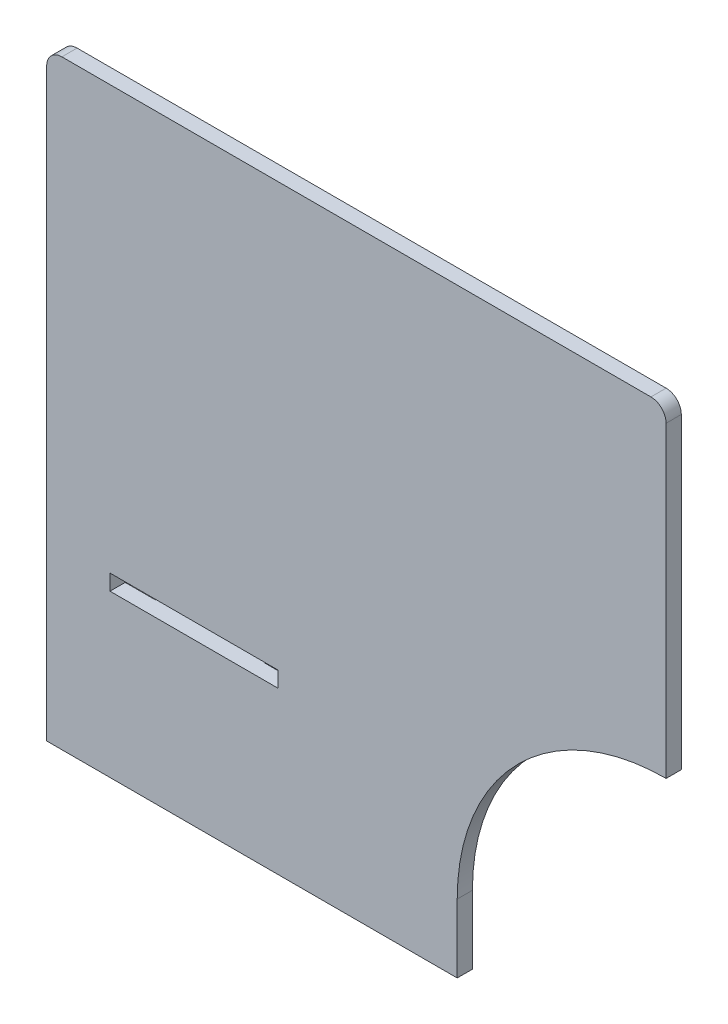
SolidWorks part; units mm, degrees
ref_plane "前视基准面" through (0, 0, 0) normal (0, 0, 1) x (1, 0, 0)
ref_plane "上视基准面" through (0, 0, 0) normal (0, 1, 0) x (1, 0, 0)
ref_plane "右视基准面" through (0, 0, 0) normal (1, 0, 0) x (0, 0, -1)
sketch "草图2" plane through (0, 0, 0) normal (0, 0, 1) x (1, 0, 0)
  line L0 (-64.1412, -71.8112) -> (-19.2042, -71.8112) construction
  line L1 (-66.1412, -9.8112) -> (-66.1412, -69.8112) construction
  line L2 (7.4028, -7.8112) -> (-64.1412, -7.8112) construction
  line L3 (9.4028, -43.2043) -> (9.4028, -9.8112) construction
  line L4 (-64.1412, -71.8112) -> (-19.2042, -71.8112)
  line L5 (-66.1412, -9.8112) -> (-66.1412, -69.8112)
  line L6 (7.4028, -7.8112) -> (-64.1412, -7.8112)
  line L7 (9.4028, -43.2043) -> (9.4028, -9.8112)
  arc A0 (7.7153, -45.1797) -> (9.4028, -43.2043) centre (7.4028, -43.2043) ccw construction
  arc A1 (7.7153, -45.1797) -> (-17.2287, -70.1237) centre (12.4028, -74.8112) ccw construction
  arc A2 (-19.2042, -71.8112) -> (-17.2287, -70.1237) centre (-19.2042, -69.8112) ccw construction
  arc A3 (-66.1412, -69.8112) -> (-64.1412, -71.8112) centre (-64.1412, -69.8112) ccw construction
  arc A4 (-64.1412, -7.8112) -> (-66.1412, -9.8112) centre (-64.1412, -9.8112) ccw construction
  arc A5 (9.4028, -9.8112) -> (7.4028, -7.8112) centre (7.4028, -9.8112) ccw construction
  arc A6 (7.7153, -45.1797) -> (9.4028, -43.2043) centre (7.4028, -43.2043) ccw
  arc A7 (7.7153, -45.1797) -> (-17.2287, -70.1237) centre (12.4028, -74.8112) ccw
  arc A8 (-19.2042, -71.8112) -> (-17.2287, -70.1237) centre (-19.2042, -69.8112) ccw
  arc A9 (-66.1412, -69.8112) -> (-64.1412, -71.8112) centre (-64.1412, -69.8112) ccw
  arc A10 (-64.1412, -7.8112) -> (-66.1412, -9.8112) centre (-64.1412, -9.8112) ccw
  arc A11 (9.4028, -9.8112) -> (7.4028, -7.8112) centre (7.4028, -9.8112) ccw
extrude "凸台-拉伸1" add sketch "草图2" against normal blind 3
sketch "草图1" plane through (0, 0, 0) normal (0, 0, 1) x (1, 0, 0)
  line L1 (12.4028, -4.8112) -> (-69.1412, -4.8112)
  line L2 (12.4028, -4.8112) -> (12.4028, -74.8112)
  line L3 (12.4028, -74.8112) -> (-69.1412, -74.8112)
  line L4 (-69.1412, -4.8112) -> (-69.1412, -74.8112)
sketch "草图3" plane through (0, 0, 0) normal (0, 0, 1) x (1, 0, 0)
  line L0 (7.4028, -7.8112) -> (-64.1412, -7.8112) construction
  line L1 (-63.1412, -10.8112) -> (6.4028, -10.8112)
  line L2 (-63.1412, -10.8112) -> (-63.1412, -68.8112)
  line L3 (-63.1412, -68.8112) -> (-20.0472, -68.8112)
  line L4 (6.4028, -10.8112) -> (6.4028, -42.3613)
  line L5 (-66.1412, -9.8112) -> (-66.1412, -69.8112) construction
  line L6 (-64.1412, -71.8112) -> (-19.2042, -71.8112) construction
  line L7 (9.4028, -43.2043) -> (9.4028, -9.8112) construction
  arc A0 (6.4028, -42.3613) -> (-20.0472, -68.8112) centre (12.4028, -74.8112) ccw
  arc A1 (7.7153, -45.1797) -> (-17.2287, -70.1237) centre (12.4028, -74.8112) ccw construction
  dimension "D1" = 3
  dimension "D5" = 3
  dimension "D2" = 3
  dimension "D3" = 3
  dimension "D4" = 3
extrude "切除-拉伸1" cut sketch "草图3" against normal blind 3
fillet "圆角1" radius 2 5 edges at (-20.0472, -68.8112, -1.5) (-63.1412, -68.8112, -1.5) (6.4028, -42.3613, -1.5) (6.4028, -10.8112, -1.5) (-63.1412, -10.8112, -1.5)
extrude "凸台-拉伸2" add sketch "草图1" along normal blind 2
sketch "草图4" plane through (0, 0, 2) normal (0, 0, 1) x (1, 0, 0)
  line L1 (-60.8097, -60.4975) -> (-38.7176, -60.4975)
  line L2 (-60.8097, -60.4975) -> (-60.8097, -62.5686)
  line L3 (-60.8097, -62.5686) -> (-38.7176, -62.5686)
  line L4 (-38.7176, -60.4975) -> (-38.7176, -62.5686)
extrude "切除-拉伸2" cut sketch "草图4" against normal blind 8
sketch "草图5" plane through (0, 0, 0) normal (0, 0, -1) x (-1, 0, 0)
  line L0 (38.7176, -62.5686) -> (60.8097, -62.5686) construction
  line L1 (56.8247, -62.5686) -> (42.4595, -62.5686)
  line L2 (56.8247, -62.5686) -> (56.8247, -64.4252)
  line L3 (56.8247, -64.4252) -> (42.4595, -64.4252)
  line L4 (42.4595, -62.5686) -> (42.4595, -64.4252)
extrude "凸台-拉伸3" add sketch "草图5" along normal blind 10
sketch "草图6" plane through (0, -62.5686, 0) normal (0, 1, 0) x (1, 0, 0)
  line L0 (-42.4595, 3) -> (-39.4438, 6.0157)
  line L1 (7.4028, 3) -> (-64.1412, 3) construction
  line L2 (-42.4595, 10) -> (-42.4595, 0) construction
  line L3 (-39.4438, 6.0157) -> (-39.4438, 10.5274)
  line L4 (-39.4438, 10.5274) -> (-60.0191, 10.5274)
  line L5 (-60.0191, 10.5274) -> (-60.0191, 6.0157)
  line L6 (-60.0191, 6.0157) -> (-57.0034, 3)
  line L7 (-57.0034, 3) -> (-42.4595, 3)
extrude "凸台-拉伸4" add sketch "草图6" against normal up to surface (1.8566 mm away) up to face at (-49.6421, -64.4252, -5)
fillet "圆角2" radius 4 1 edges at (-49.6421, -64.4252, 0)
sketch "草图7" plane through (0, 0, 2) normal (0, 0, 1) x (1, 0, 0)
  circle A0 centre (12.4028, -74.8112) radius 27.5
  dimension "D1" = 55
extrude "切除-拉伸3" cut sketch "草图7" against normal blind 7
sketch "草图8" plane through (0, -74.8112, 0) normal (0, -1, 0) x (1, 0, 0)
  line L1 (-69.1412, 2) -> (-15.0972, 2)
  line L2 (-69.1412, 2) -> (-69.1412, 0)
  line L3 (-69.1412, 0) -> (-15.0972, 0)
  line L4 (-15.0972, 2) -> (-15.0972, 0)
extrude "凸台-拉伸5" add sketch "草图8" along normal blind 9
fillet "圆角3" radius 2 2 edges at (12.4028, -4.8112, 1) (-69.1412, -4.8112, 1)
